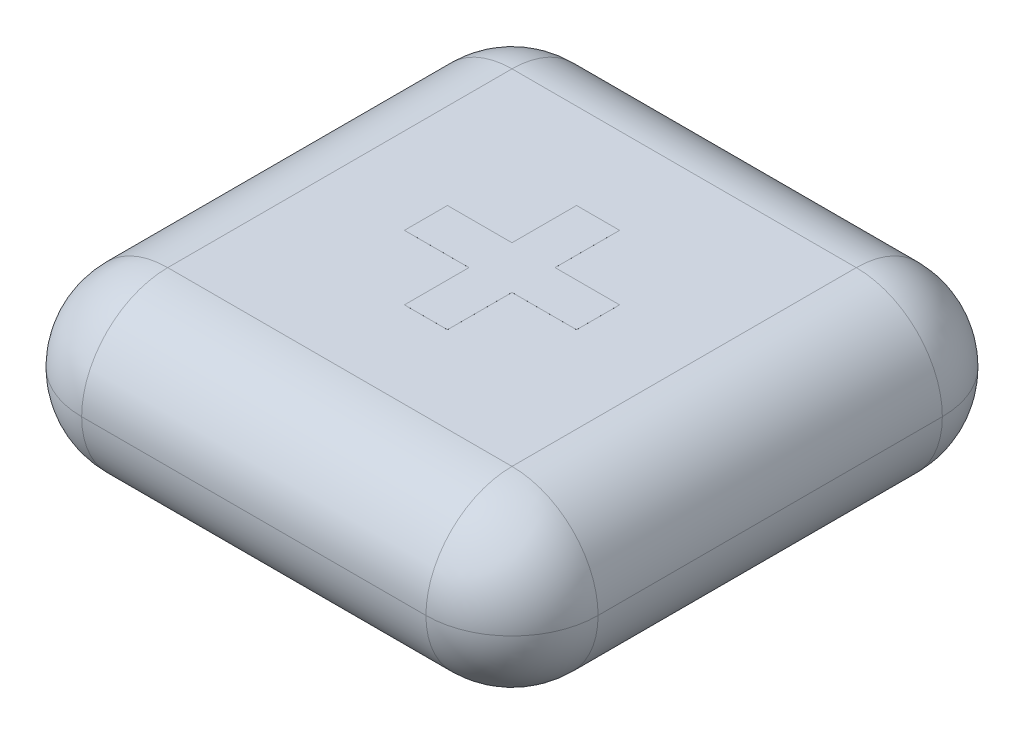
SolidWorks part; units mm, degrees
ref_plane "Front Plane" through (0, 0, 0) normal (0, 0, 1) x (1, 0, 0)
ref_plane "Top Plane" through (0, 0, 0) normal (0, 1, 0) x (1, 0, 0)
ref_plane "Right Plane" through (0, 0, 0) normal (1, 0, 0) x (0, 0, -1)
sketch "Sketch1" plane through (0, 0, 0) normal (0, 1, 0) x (1, 0, 0)
  line L1 (-38.1, -38.1) -> (38.1, -38.1)
  line L2 (-38.1, -38.1) -> (-38.1, 38.1)
  line L3 (-38.1, 38.1) -> (38.1, 38.1)
  line L4 (38.1, -38.1) -> (38.1, 38.1)
  line L5 (-38.1, -38.1) -> (38.1, 38.1) construction
  line L6 (-38.1, 38.1) -> (38.1, -38.1) construction
  point P0 (0, 0)
  dimension "D1" = 76.2
  dimension "D2" = 76.2
extrude "Boss-Extrude1" add sketch "Sketch1" along normal blind 25.4 contours L2 L1 L4 L3
fillet "Fillet1" radius 12.7 8 edges at (-38.1, 0, 0) (0, 0, 38.1) (38.1, 0, 0) (0, 0, -38.1) (38.1, 25.4, 0) (0, 25.4, 38.1) (-38.1, 25.4, 0) (0, 25.4, -38.1)
sketch "Sketch2" plane through (0, 25.4, 0) normal (0, 1, 0) x (1, 0, 0)
  line L1 (-3.175, -12.7) -> (3.175, -12.7)
  line L2 (-3.175, -12.7) -> (-3.175, 12.7)
  line L3 (-3.175, 12.7) -> (3.175, 12.7)
  line L4 (3.175, -12.7) -> (3.175, 12.7)
  line L5 (-3.175, -12.7) -> (3.175, 12.7) construction
  line L6 (-3.175, 12.7) -> (3.175, -12.7) construction
  line L7 (-12.7, -3.175) -> (12.7, -3.175)
  line L8 (-12.7, -3.175) -> (-12.7, 3.175)
  line L9 (-12.7, 3.175) -> (12.7, 3.175)
  line L10 (12.7, -3.175) -> (12.7, 3.175)
  line L11 (-12.7, -3.175) -> (12.7, 3.175) construction
  line L12 (-12.7, 3.175) -> (12.7, -3.175) construction
  point P0 (0, 0)
  point P6 (0, 0)
  dimension "D1" = 25.4
  dimension "D2" = 6.35
extrude "Boss-Extrude2" add sketch "Sketch2" along normal blind 0.0025 contours L7 L10 L9 L4 | L9 L8 L7 L2 | L4 L3 L2 L1 region at (-7.9375, 25.4, 0) region at (7.9375, 25.4, 0)
